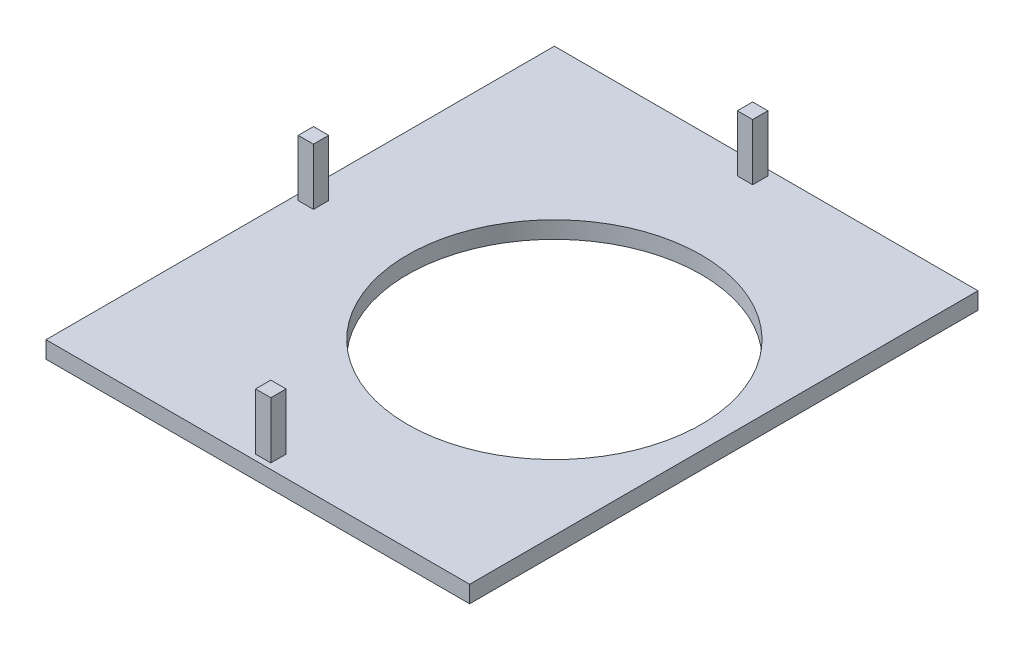
SolidWorks part; units mm, degrees
material "Custom Plastic"
ref_plane "Front Plane" through (0, 0, 0) normal (0, 0, 1) x (1, 0, 0)
ref_plane "Top Plane" through (0, 0, 0) normal (0, 1, 0) x (1, 0, 0)
ref_plane "Right Plane" through (0, 0, 0) normal (1, 0, 0) x (0, 0, -1)
sketch "Sketch1" plane through (0, 0, 0) normal (0, 1, 0) x (1, 0, 0)
  line L1 (0, 0) -> (75, 0)
  line L2 (0, 0) -> (0, -90)
  line L3 (0, -90) -> (75, -90)
  line L4 (75, 0) -> (75, -90)
  dimension "D1" = 75
  dimension "D2" = 90
extrude "Boss-Extrude1" add sketch "Sketch1" along normal blind 3
sketch "Sketch2" plane through (0, 3, 0) normal (0, 1, 0) x (1, 0, 0)
  line L0 (75, 0) -> (0, 0) construction
  line L1 (36.1, -1) -> (38.8, -1)
  line L2 (36.1, -1) -> (36.1, -3.7)
  line L3 (36.1, -3.7) -> (38.8, -3.7)
  line L4 (38.8, -1) -> (38.8, -3.7)
  line L5 (1, -43.65) -> (3.7, -43.65)
  line L6 (1, -43.65) -> (1, -46.35)
  line L7 (1, -46.35) -> (3.7, -46.35)
  line L8 (3.7, -43.65) -> (3.7, -46.35)
  line L9 (36.1, -86.3) -> (38.8, -86.3)
  line L10 (36.1, -86.3) -> (36.1, -89)
  line L11 (36.1, -89) -> (38.8, -89)
  line L12 (38.8, -86.3) -> (38.8, -89)
  line L13 (0, -90) -> (75, -90) construction
  line L14 (0, 0) -> (0, -90) construction
  line L15 (2.35, -43.65) -> (2.35, 0) construction
  line L16 (2.35, -46.35) -> (2.35, -90) construction
  dimension "D1" = 2.7
  dimension "D2" = 1
  dimension "D3" = 1
  dimension "D4" = 36.1
  dimension "D5" = 1
extrude "Boss-Extrude2" add sketch "Sketch2" along normal blind 10
sketch "Sketch3" plane through (0, 3, 0) normal (0, 1, 0) x (1, 0, 0)
  line L0 (0, 0) -> (0, -90) construction
  circle A0 centre (45, -45) radius 26
  dimension "D1" = 52
  dimension "D2" = 45
extrude "Cut-Extrude1" cut sketch "Sketch3" against normal up to surface (3 mm away) up to face at (37.5, 0, 45)
